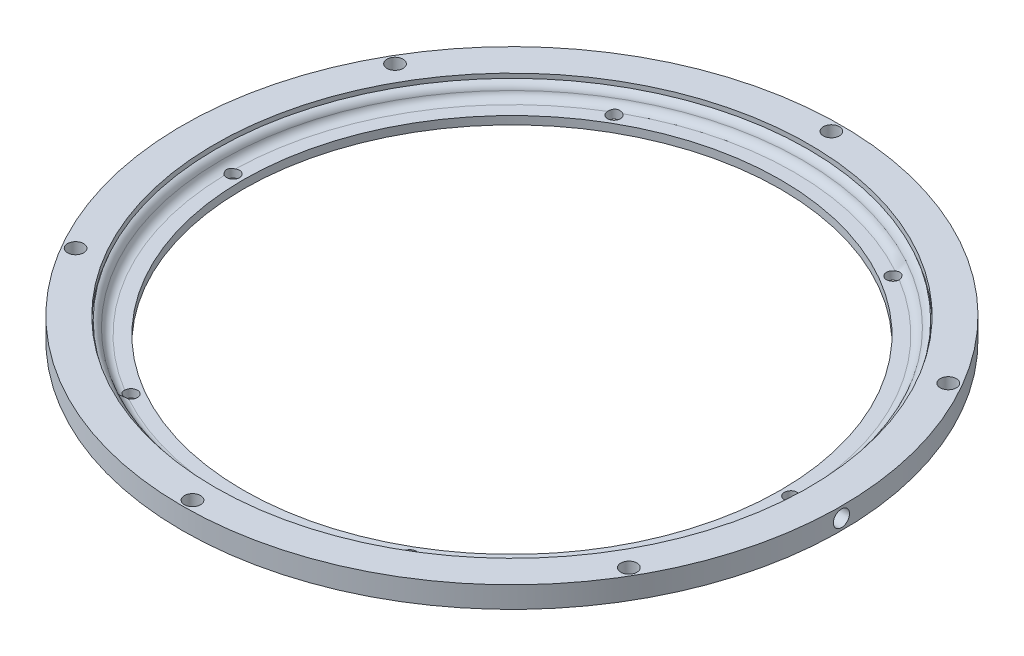
SolidWorks part; units mm, degrees
note: '?' marks a value the reader was unsure of.
ref_plane "Front" through (0, 0, 0) normal (0, 0, 1) x (1, 0, 0)
ref_plane "Top" through (0, 0, 0) normal (0, 1, 0) x (1, 0, 0)
ref_plane "Right" through (0, 0, 0) normal (1, 0, 0) x (0, 0, -1)
ref_axis "Axis1" through (0, 12.8289, 0) along (0, -1, 0)?
sketch "Sketch1" plane through (0, 0, 0) normal (0, 0, 1) x (1, 0, 0)
  line L0 (0, 8.551) -> (0, -4.9357) construction
  line L1 (162.5, 12.2174) -> (162.5, 1.6954)
  line L2 (162.5, 12.2174) -> (146.5, 12.2174)
  line L3 (146.5, 12.2174) -> (146.5, 9.0402)
  line L4 (149.5, 1.6954) -> (162.5, 1.6954)
  line L5 (132.516, 0) -> (148, 0)
  line L6 (132.516, 0) -> (162.5, 12.2174) construction
  line L7 (149.5, 1.6954) -> (149.5, 3.7334)
  line L9 (132.516, 4) -> (132.516, 0)
  line L10 (146.5, 9.0402) -> (149.5, 3.7334) construction
  line L11 (148, 0) -> (148, 3.048)
  line L12 (146, 10.3485) -> (146, 8.8172)
  line L13 (139.0875, 4) -> (132.516, 4)
  arc A0 (146, 8.8172) -> (148, 3.048) centre (147.508, 6.1087) ccw
  arc A1 (146, 10.3485) -> (143.1369, 7.1781) centre (147.508, 6.1087) ccw
  arc A2 (139.0875, 4) -> (143.1369, 7.1781) centre (139.0875, 8.1689) ccw
  arc A3 (149.5, 3.7334) -> (146.5, 9.0402) centre (147.508, 6.1087) ccw
  point P17 (148, 6.3868)
  dimension "D8" = 6.2
  dimension "D9" = 9
  dimension "D2" = 12.2174
  dimension "D3" = 29.984
  dimension "D4" = 16
  dimension "D5" = 10.522
  dimension "D6" = 13
  dimension "D7" = 4
  dimension "D10" = 0.5
  dimension "D11" = 325
  dimension "D12" = 278.175
  dimension "D13" = 1.6954
  dimension "D14" = 265.032
revolve "Revolve2" add sketch "Sketch1" angle 360 about L0
sketch "Sketch2" plane through (0, 0, 0) normal (0, -1, 0) x (1, 0, 0)
  line L0 (0, 0) -> (167.0886, 0) construction
  line L1 (0, 0) -> (86.0025, -148.9607) construction
  line L2 (132.516, 4.1036) -> (132.516, -4.7686) construction
  line L3 (134.516, 3.5121) -> (134.516, -5.9515) construction
  line L4 (137.5, 0) -> (140.484, 0) construction
  line L5 (134.516, 0) -> (137.5, 0) construction
  line L6 (139.657, -6.35) -> (135.2215, -6.35) construction
  line L7 (73.5238, -114.647) -> (75.5358, -118.1318) construction
  arc A0 (75.0109, -111.6598) -> (134.2057, -9.1314) centre (0, 0) ccw
  arc A1 (78.3389, -116.6138) -> (140.1599, -9.5366) centre (0, 0) ccw
  circle A2 centre (0, 0) radius 137.5 construction
  circle A3 centre (0, 0) radius 132.516 construction
  arc A4 (140.1599, -9.5366) -> (134.2057, -9.1314) centre (137.1828, -9.334) ccw
  arc A5 (75.0109, -111.6598) -> (78.3389, -116.6138) centre (76.6749, -114.1368) ccw
  dimension "D2" = 275
  dimension "D1" = 60
  dimension "D3" = 2
  dimension "D4" = 6.35
  dimension "D5" = 6.35
extrude "Cut-Extrude1" cut sketch "Sketch2" against normal offset from surface (0.3132 mm away) 3.81
pattern_circular "CirPattern1" count 6 over 360 about axis through (0, 0, 0) along (0, 1, 0) of "Cut-Extrude1"
sketch "Sketch3" plane through (0, 1.6954, 0) normal (0, -1, 0) x (1, 0, 0)
  line L0 (0, 0) -> (149.5, 86.3139) construction
  line L1 (0, 0) -> (154.2972, -89.0835) construction
  line L2 (0, 0) -> (63.0511, 0) construction
  line L3 (142.7957, 73.2777) -> (134.9914, 68.7719)
  line L4 (134.9914, -68.7719) -> (142.7957, -73.2777)
  line L5 (162.5, 4.9183) -> (162.5, -33.5059) construction
  line L6 (160.5, 8.5668) -> (160.5, -35.0892) construction
  line L7 (151.5, 7.4564) -> (151.5, -22.8744) construction
  line L8 (149.5, -1.1233) -> (149.5, -18.1031) construction
  arc A0 (142.7957, -73.2777) -> (142.7957, 73.2777) centre (0, 0) ccw
  arc A1 (134.9914, -68.7719) -> (134.9914, 68.7719) centre (0, 0) ccw
  circle A2 centre (0, 0) radius 149.5 construction
  circle A3 centre (0, 0) radius 162.5 construction
  dimension "D1" = 60
  dimension "D2" = 30
  dimension "D3" = 7.9375
  dimension "D4" = 7.9375
  dimension "D5" = 2
  dimension "D6" = 2
extrude "Cut-Extrude2" cut sketch "Sketch3" against normal blind 10
pattern_circular "CirPattern2" count 6 over 360 about axis through (0, 0, 0) along (0, 1, 0) of "Cut-Extrude2"
sketch "Sketch5" plane through (0, 4, 0) normal (0, 1, 0) x (-1, 0, 0)
  line L0 (0, 0) -> (-68.75, -119.0785) construction
  line L1 (17.7406, -10.2426) -> (-18.7249, 10.8108) construction
  line L2 (0, 0) -> (0, -87.4239) construction
  circle A0 centre (-68.75, -119.0785) radius 3.175
  dimension "D1" = 6.35
  dimension "D2" = 275
  dimension "D3" = 30
extrude "Cut-Extrude3" cut sketch "Sketch5" against normal through all and the other way through all
pattern_circular "CirPattern3" count 6 over 360 about axis through (0, 0, 0) along (0, 1, 0) of "Cut-Extrude3"
sketch "Sketch8" plane through (0, 0, 0) normal (0, 0, 1) x (1, 0, 0)
  line L1 (151.5, 11.6954) -> (160.5, 11.6954)
  line L2 (151.5, 11.6954) -> (151.5, 1.6954)
  line L3 (151.5, 1.6954) -> (160.5, 1.6954)
  line L4 (160.5, 11.6954) -> (160.5, 1.6954)
  line L5 (142.7957, 1.6954) -> (160.5, 1.6954) construction
  line L6 (142.7957, 11.6954) -> (160.5, 11.6954) construction
  line L7 (151.5, 1.6954) -> (151.5, 11.6954) construction
  line L8 (160.5, 1.6954) -> (160.5, 11.6954) construction
  line L9 (0, 29.5183) -> (0, -14.1535) construction
revolve "Revolve3" add sketch "Sketch8" angle 5 mid plane about L9
sketch "Sketch7" plane through (0, 0, 0) normal (0, 0, 1) x (1, 0, 0)
  line L0 (162.5, 6.9564) -> (169.66, 6.9564) construction
  line L1 (162.5, 1.6954) -> (162.5, 12.2174) construction
  line L2 (148, 0) -> (148, 3.048) construction
  line L3 (162.5, 6.9564) -> (148, 6.9564)
  line L4 (162.5, 6.9564) -> (162.5, 10.9251)
  line L5 (162.5, 10.9251) -> (148, 10.9251)
  line L6 (148, 6.9564) -> (148, 10.9251)
  dimension "D1" = 7.9375
revolve "Cut-Revolve3" cut sketch "Sketch7" angle 360 about L0
sketch "Sketch9" plane through (0, 12.2174, 0) normal (0, 1, 0) x (-1, 0, 0)
  line L0 (0, 0) -> (-153.3926, -88.5612) construction
  line L1 (0, 0) -> (-88.4835, 0) construction
  circle A0 centre (-136.399, -78.75) radius 3.9687
  circle A1 centre (0, 0) radius 157.5 construction
  dimension "D2" = 315
  dimension "D3" = 7.9375
  dimension "D1" = 30
extrude "Cut-Extrude4" cut sketch "Sketch9" against normal through all
pattern_circular "CirPattern4" count 6 over 360 about axis through (0, 0, 0) along (0, 1, 0) of "Cut-Extrude4"
sketch "Sketch10" plane through (0, 0, 0) normal (0, 0, 1) x (1, 0, 0)
  line L0 (168.7798, 6.9564) -> (150.847, 6.9564) construction
  line L1 (162.5, 6.9564) -> (169.66, 6.9564) construction
  line L2 (168.85, 9.9564) -> (168.85, 10.9251)
  line L3 (168.85, 10.9251) -> (181.55, 10.9251) construction
  line L4 (181.55, 10.9251) -> (181.55, 6.9564)
  line L5 (181.55, 6.9564) -> (171.85, 6.9564)
  line L6 (168.85, 10.9251) -> (169.5556, 9.7031)
  line L7 (169.5556, 9.7031) -> (170.2611, 10.9251)
  line L8 (170.2611, 10.9251) -> (170.9667, 9.7031)
  line L9 (170.9667, 9.7031) -> (171.6722, 10.9251)
  line L10 (168.4966, 9.7031) -> (178.8498, 9.7031) construction
  line L11 (169.5556, 9.7031) -> (169.5556, 9.7676) construction
  line L12 (162.5, 10.9251) -> (162.5, 12.2174) construction
  line L13 (171.6722, 10.9251) -> (172.3778, 9.7031)
  line L14 (172.3778, 9.7031) -> (173.0833, 10.9251)
  line L15 (173.0833, 10.9251) -> (173.7889, 9.7031)
  line L16 (173.7889, 9.7031) -> (174.4944, 10.9251)
  line L17 (174.4944, 10.9251) -> (175.2, 9.7031)
  line L18 (175.2, 9.7031) -> (175.9056, 10.9251)
  line L19 (175.9056, 10.9251) -> (176.6111, 9.7031)
  line L20 (176.6111, 9.7031) -> (177.3167, 10.9251)
  line L21 (177.3167, 10.9251) -> (178.0222, 9.7031)
  line L22 (178.0222, 9.7031) -> (178.7278, 10.9251)
  line L23 (178.7278, 10.9251) -> (179.4333, 9.7031)
  line L24 (179.4333, 9.7031) -> (180.1389, 10.9251)
  line L25 (180.1389, 10.9251) -> (181.55, 10.9251)
  line L26 (168.85, 9.9564) -> (171.85, 6.9564)
  dimension "D1" = 12.7
  dimension "D2" = 60
  dimension "D3" = 1.4111
  dimension "D4" = 7.9375
  dimension "D5" = 6.35
  dimension "D6" = 135
  dimension "D7" = 6
revolve "Revolve4" [suppressed] add sketch "Sketch10" angle 360 about L0
sketch "Sketch11" [suppressed] plane through (181.55, 0, 0) normal (1, 0, 0) x (0, 0, -1)
  line L1 (1.3748, 9.3376) -> (-1.3748, 9.3376)
  line L2 (-1.3748, 9.3376) -> (-2.7496, 6.9564)
  line L3 (-2.7496, 6.9564) -> (-1.3748, 4.5751)
  line L4 (-1.3748, 4.5751) -> (1.3748, 4.5751)
  line L5 (1.3748, 4.5751) -> (2.7496, 6.9564)
  line L6 (2.7496, 6.9564) -> (1.3748, 9.3376)
  circle A0 centre (0, 6.9564) radius 2.3813 construction
  circle A1 centre (0, 6.9564) radius 3.9687 construction
  dimension "D1" = 4.7625
extrude "Cut-Extrude5" [suppressed] cut sketch "Sketch11" against normal blind 5.08
